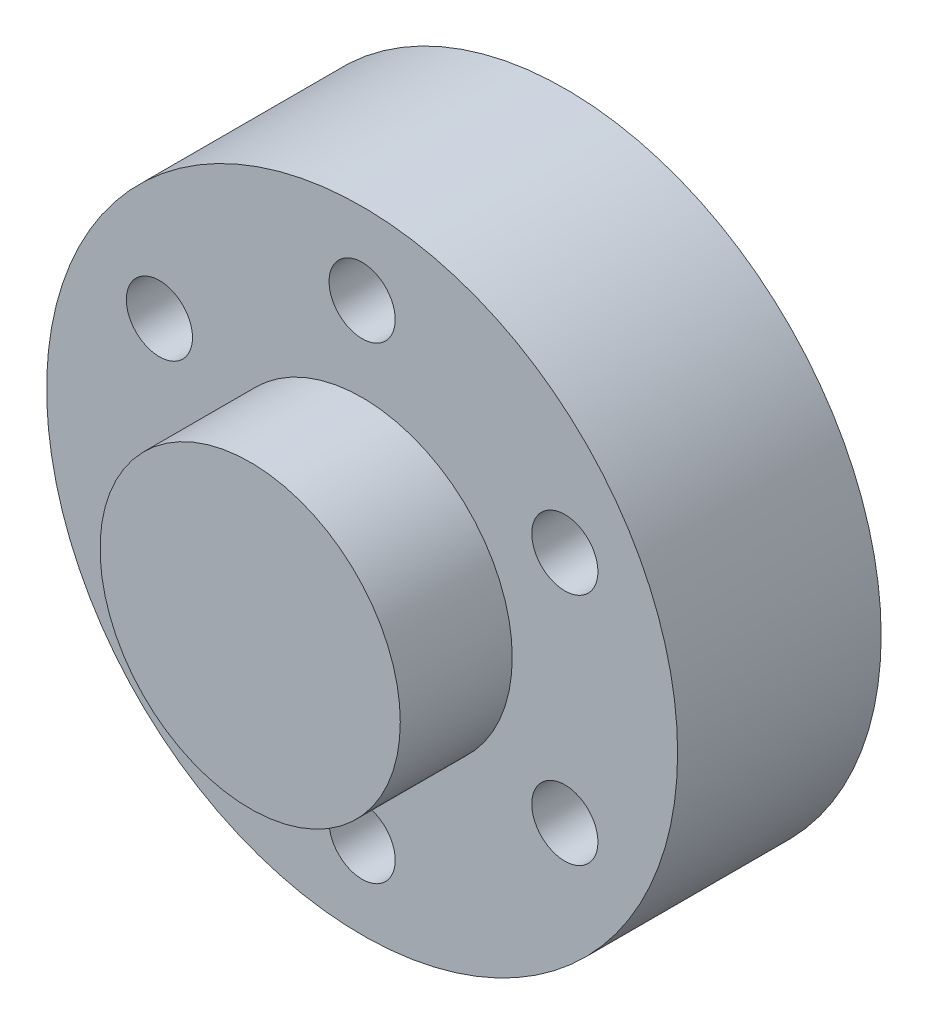
SolidWorks part; units mm, degrees
ref_plane "Front Plane" through (0, 0, 0) normal (0, 0, 1) x (1, 0, 0)
ref_plane "Top Plane" through (0, 0, 0) normal (0, 1, 0) x (1, 0, 0)
ref_plane "Right Plane" through (0, 0, 0) normal (1, 0, 0) x (0, 0, -1)
sketch "Sketch2" plane through (0, 0, 0) normal (0, 0, 1) x (1, 0, 0)
  line L0 (0, 20.3178) -> (0, -21.083) construction
  circle A0 centre (0, 0) radius 9.5
  circle A1 centre (0, 0) radius 11.5 construction
  circle A3 centre (0, 0) radius 15.5
  circle A4 centre (0, 11.5) radius 1.625
  circle A10 centre (9.9593, 5.75) radius 1.625
  circle A11 centre (9.9593, -5.75) radius 1.625
  circle A12 centre (0, -11.5) radius 1.625
  circle A13 centre (-9.9593, -5.75) radius 1.625
  circle A14 centre (-9.9593, 5.75) radius 1.625
  point P21 (1.7321, -1)
  point P22 (0.866, -0.5)
  point P23 (0, 0)
  dimension "D1" = 19
  dimension "D2" = 6
  dimension "D3" = 23
  dimension "D4" = 31
  dimension "D5" = 3.25
extrude "Boss-Extrude1" add sketch "Sketch2" along normal blind 10 contours A3 A14 A13 A12 A11 A10 A4 A0 | A0 region at (0, 0, 0) region at (-15.0616, 0, 0)
sketch "Sketch3" plane through (0, 0, 10) normal (0, 0, 1) x (1, 0, 0)
  circle A0 centre (0, 0) radius 7.375
  dimension "D1" = 14.75
extrude "Boss-Extrude2" add sketch "Sketch3" along normal blind 5.5
sketch "Sketch6" plane through (0, 0, 0) normal (0, 0, -1) x (-1, 0, 0)
  circle A0 centre (0, 0) radius 7.375
  dimension "D1" = 14.75
extrude "Boss-Extrude4" add sketch "Sketch6" along normal blind 5.5 contours A0
sketch "Sketch7" plane through (0, 0, -5.5) normal (0, 0, -1) x (-1, 0, 0)
  circle A0 centre (0, 0) radius 2
  dimension "D1" = 4
extrude "Boss-Extrude5" add sketch "Sketch7" along normal blind 1
fillet "Fillet2" radius 0.05 1 edges at (-2, 0, -6.5)
sketch "Sketch9" plane through (0, 0, -6.5) normal (0, 0, -1) x (-1, 0, 0)
  line L1 (-1.2247, 1.25) -> (1.2247, 1.25)
  arc A0 (-1.2247, 1.25) -> (1.2247, 1.25) centre (0, 0) ccw
  circle A1 centre (0, -0.25) radius 1.5 construction
  dimension "D1" = 3.5
  dimension "D2" = 3
extrude "Cut-Extrude1" cut sketch "Sketch9" against normal blind 11
